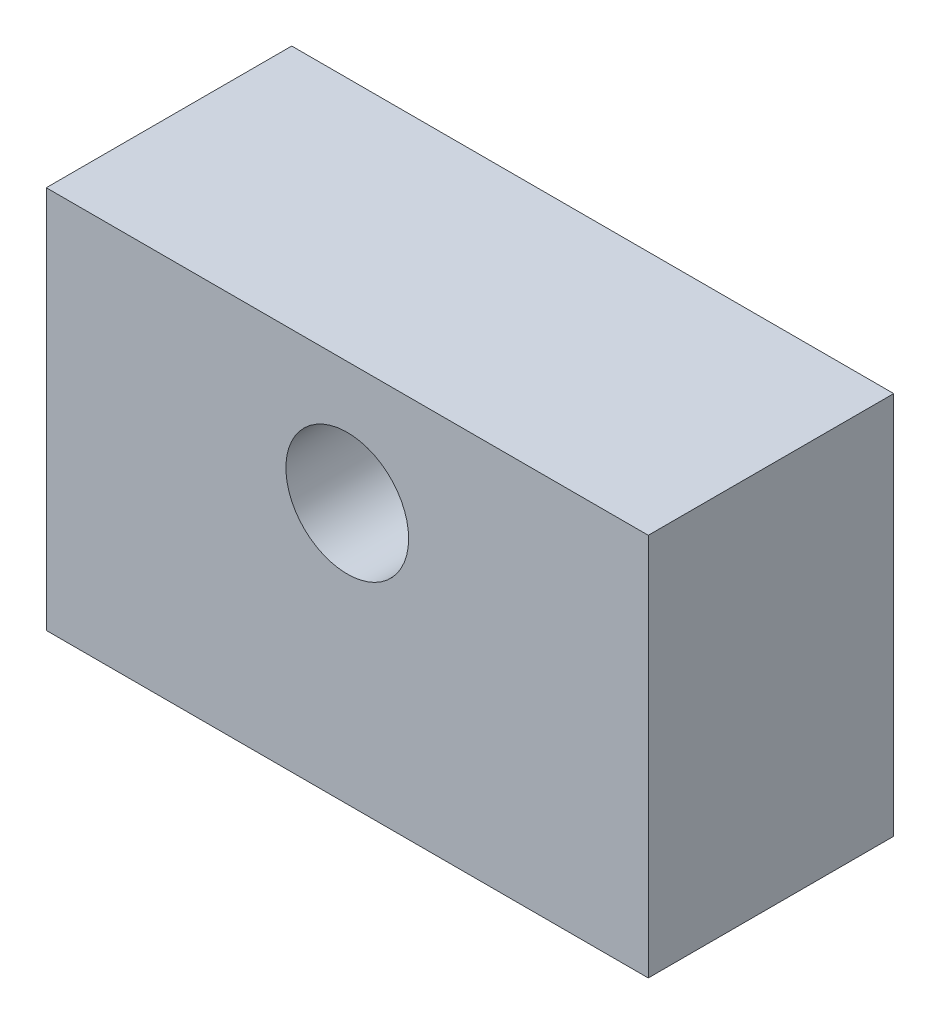
SolidWorks part; units mm, degrees
material "1060 Alloy"
ref_plane "Front" through (0, 0, 0) normal (0, 0, 1) x (1, 0, 0)
ref_plane "Top" through (0, 0, 0) normal (0, 1, 0) x (1, 0, 0)
ref_plane "Right" through (0, 0, 0) normal (1, 0, 0) x (0, 0, -1)
sketch "Sketch3" plane through (0, 0, 0) normal (0, 0, 1) x (1, 0, 0)
  line L0 (-0.127, -6.35) -> (30.1755, -6.35)
  line L1 (0, 0) -> (31.1484, 0)
  line L2 (0, 0) -> (0, -19.8376)
  line L3 (0, -19.8376) -> (31.1484, -19.8376)
  line L4 (31.1484, 0) -> (31.1484, -19.8376)
  line L5 (15.5742, -19.8376) -> (15.5742, 0) construction
  line L6 (15.5742, -6.35) -> (8.0621, -19.3614) construction
  line L15 (12.5496, -11.5887) -> (15.5742, -13.335) construction
  line L16 (15.5742, -6.35) -> (22.9274, -19.0862) construction
  circle A0 centre (15.5742, -6.35) radius 6.0492 construction
  point P14 (0, -6.35)
  point P17 (9.525, -6.35)
  point P19 (31.1484, -6.35)
  point P20 (7.7871, -19.8376)
  point P24 (23.3613, -19.8376)
  dimension "D2" = 6.35
  dimension "D6" = 3.4925
  dimension "D3" = 60
  dimension "D1" = 9.525
  dimension "D4" = 9.525
  dimension "D5" = 60
extrude "Boss-Extrude1" add sketch "Sketch3" along normal mid plane 12.7
sketch "Sketch4" plane through (0, 0, 0) normal (-1, 0, 0) x (0, 0, 1)
  circle A0 centre (0, -6.35) radius 3.175
  dimension "D1" = 6.35
extrude "Cut-Extrude1" cut sketch "Sketch4" against normal blind 9.525
ref_plane "Plane1" through (7.7871, -19.8376, 0) normal (-0.5, -0.866, 0) x (-0.866, 0.5, 0)
ref_plane "Mirror Plane" through (15.5742, 0, 0) normal (-1, 0, 0) x (0, 0, 1)
sketch "Sketch5" plane through (7.7871, -19.8376, 0) normal (-0.5, -0.866, 0) x (-0.866, 0.5, 0)
  circle A0 centre (0, 0) radius 3.175
  dimension "D1" = 6.35
extrude "Cut-Extrude5" cut sketch "Sketch5" against normal blind 9.525 and the other way up to next
sketch "Sketch6" plane through (0, 0, 6.35) normal (0, 0, -1) x (-1, 0, 0)
  circle A0 centre (-15.5742, -6.35) radius 3.175
  dimension "D1" = 6.35
extrude "Cut-Extrude6" cut sketch "Sketch6" along normal blind 9.525
mirror "Mirror1" about plane through (15.5742, 0, 0) normal (-1, 0, 0) of "Cut-Extrude5"
equation "\"truss_member_od\" = .25in"
equation "\"truss_member_id\" = 0in"
equation "\"truss_member_L1\" = 2.75in"
equation "\"connector_hole_depth\" = .375in"
equation "\"D1@Boss-Extrude1\"=\"truss_member_od\"*2"
equation "\"D6@Sketch3\"=\"truss_member_od\"/2*1.1"
equation "\"D1@Sketch4\"=\"truss_member_od\""
equation "\"D1@Cut-Extrude1\"=\"connector_hole_depth\""
equation "\"D1@Sketch3\"=\"connector_hole_depth\""
equation "\"D4@Sketch3\"=\"connector_hole_depth\""
equation "\"D1@Sketch5\"=\"truss_member_od\""
equation "\"D1@Cut-Extrude5\"=\"connector_hole_depth\""
equation "\"D1@Cut-Extrude6\"=\"connector_hole_depth\""
equation "\"D1@Sketch6\"=\"truss_member_od\""
